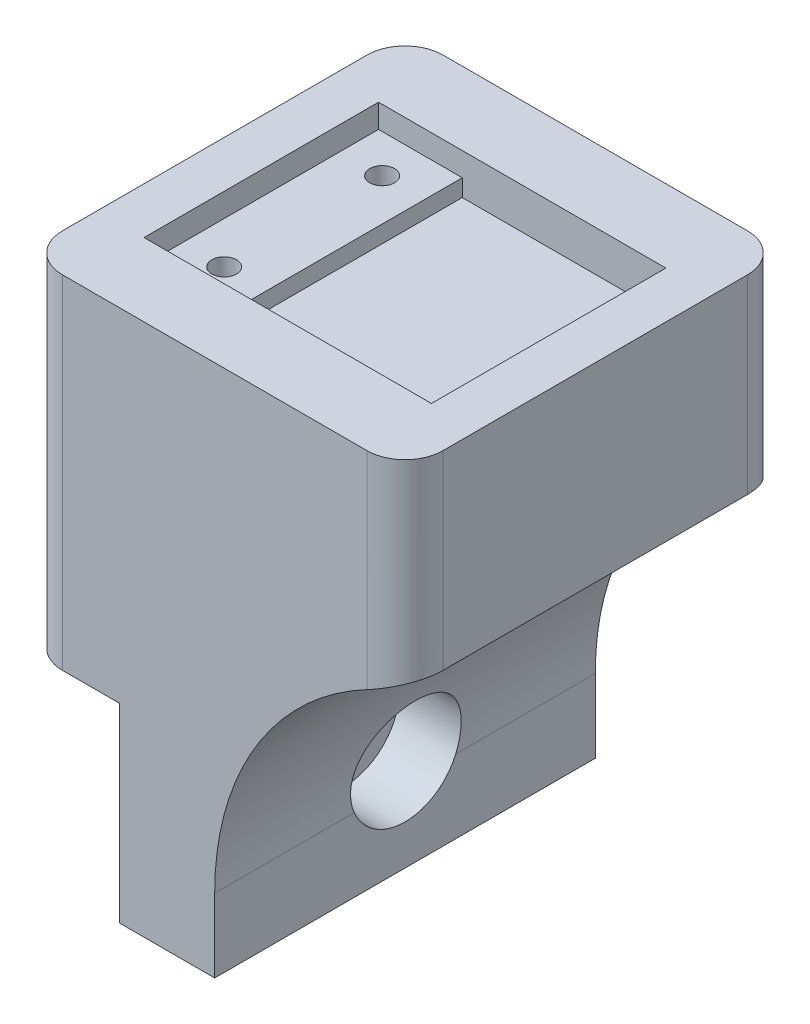
SolidWorks part; units mm, degrees
ref_plane "Front Plane" through (0, 0, 0) normal (0, 0, 1) x (1, 0, 0)
ref_plane "Top Plane" through (0, 0, 0) normal (0, 1, 0) x (1, 0, 0)
ref_plane "Right Plane" through (0, 0, 0) normal (1, 0, 0) x (0, 0, -1)
sketch "Profile" plane through (0, 0, 0) normal (0, 0, 1) x (1, 0, 0)
  line L1 (-6.35, 22.86) -> (6.35, 22.86)
  line L2 (-6.35, 22.86) -> (-6.35, 0)
  line L3 (-6.35, 0) -> (6.35, 0)
  line L4 (6.35, 22.86) -> (6.35, 0)
  line L5 (0, 0) -> (6.35, 0)
  line L6 (0, 0) -> (0, -12.7)
  line L7 (0, -12.7) -> (6.35, -12.7)
  line L8 (6.35, 0) -> (6.35, -12.7)
  dimension "D1" = 22.86
  dimension "D2" = 12.7
  dimension "D3" = 6.35
  dimension "D4" = 12.7
extrude "Boss-Extrude1" add sketch "Profile" along normal mid plane 25.4 contours L4 L1 L2 L3 | L8 L3 L6 L7 region at (0, 11.43, 0) region at (3.175, -6.35, 0)
sketch "ScrewHole" plane through (0, 0, 0) normal (-1, 0, 0) x (0, 0, 1)
  line L0 (12.7, 0) -> (12.7, -12.7) construction
  line L1 (12.7, -12.7) -> (-12.7, -12.7) construction
  circle A0 centre (0, -6.35) radius 2.159
  point P5 (12.7, -6.35)
  point P10 (0, -12.7)
  dimension "D1" = 4.318
extrude "Cut-Extrude1" cut sketch "ScrewHole" against normal through all both
sketch "Sketch3" plane through (6.35, 0, 0) normal (1, 0, 0) x (0, 0, -1)
  circle A0 centre (0, -6.35) radius 2.159 construction
  circle A1 centre (0, -6.35) radius 2.159
  circle A2 centre (0, -6.35) radius 3.683
  dimension "D1" = 7.366
extrude "Cut-Extrude2" cut sketch "Sketch3" against normal blind 4.064
sketch "Sketch4" plane through (6.35, 0, 0) normal (1, 0, 0) x (0, 0, -1)
  line L0 (12.7, 22.86) -> (12.7, -12.7) construction
  line L1 (-12.7, 22.86) -> (12.7, 22.86)
  line L2 (-12.7, 22.86) -> (-12.7, 10.16)
  line L3 (-12.7, 10.16) -> (12.7, 10.16)
  line L4 (12.7, 22.86) -> (12.7, 10.16)
  dimension "D1" = 12.7
extrude "Boss-Extrude2" add sketch "Sketch4" along normal blind 12.7
sketch "Sketch6" plane through (0, 22.86, 0) normal (0, 1, 0) x (1, 0, 0)
  line L0 (-6.35, -12.7) -> (-6.35, 12.7) construction
  line L1 (-3.2385, 7.8232) -> (15.9385, 7.8232)
  line L2 (-3.2385, 7.8232) -> (-3.2385, -7.8232)
  line L3 (-3.2385, -7.8232) -> (15.9385, -7.8232)
  line L4 (15.9385, 7.8232) -> (15.9385, -7.8232)
  line L5 (-6.35, -12.7) -> (19.05, -12.7) construction
  point P6 (-6.35, 0)
  point P7 (-3.2385, 0)
  point P10 (6.35, -12.7)
  point P11 (6.35, -7.8232)
  dimension "D1" = 19.177
  dimension "D2" = 15.6464
extrude "Cut-Extrude3" cut sketch "Sketch6" against normal blind 1.5748
sketch "Sketch7" plane through (0, 21.2852, 0) normal (0, 1, 0) x (1, 0, 0)
  line L0 (13.1445, 5.2705) -> (13.1445, -5.2705) construction
  line L1 (15.9385, -7.8232) -> (15.9385, 7.8232) construction
  line L2 (6.35, 7.8232) -> (6.35, -7.8232) construction
  line L3 (15.9385, 7.8232) -> (-3.2385, 7.8232) construction
  line L4 (-3.2385, -7.8232) -> (15.9385, -7.8232) construction
  circle A0 centre (13.1445, 5.2705) radius 0.8255
  circle A1 centre (13.1445, -5.2705) radius 0.8255
  circle A2 centre (-0.4445, -5.2705) radius 0.8255
  circle A3 centre (-0.4445, 5.2705) radius 0.8255
  point P6 (15.9385, 0)
  point P7 (13.1445, 0)
  dimension "D3" = 1.651
  dimension "D4" = 1.651
  dimension "D1" = 10.541
  dimension "D2" = 2.794
ref_plane "Plane1" through (6.35, 0, 0) normal (1, 0, 0) x (0, 0, -1)
sketch "Sketch9" plane through (0, 21.2852, 0) normal (0, 1, 0) x (1, 0, 0)
  line L0 (-3.2385, -7.8232) -> (15.9385, -7.8232) construction
  line L1 (2.3495, 7.8232) -> (15.9385, 7.8232)
  line L2 (2.3495, 7.8232) -> (2.3495, -7.8232)
  line L3 (2.3495, -7.8232) -> (15.9385, -7.8232)
  line L4 (15.9385, 7.8232) -> (15.9385, -7.8232)
  line L7 (15.9385, -7.8232) -> (15.9385, 7.8232) construction
  line L8 (-3.2385, 7.8232) -> (-3.2385, -7.8232) construction
  line L9 (15.9385, 7.8232) -> (-3.2385, 7.8232) construction
  dimension "D1" = 5.588
extrude "Cut-Extrude5" cut sketch "Sketch9" against normal blind 1.143
extrude "Cut-Extrude6" cut sketch "Sketch7" against normal blind 12.7 contours A2 | A3
fillet "Fillet1" radius 19.05 1 edges at (6.35, 10.16, 0)
fillet "Fillet2" radius 2.54 4 edges at (-6.35, 11.43, -12.7) (19.05, 16.51, -12.7) (-6.35, 11.43, 12.7) (19.05, 16.51, 12.7)
